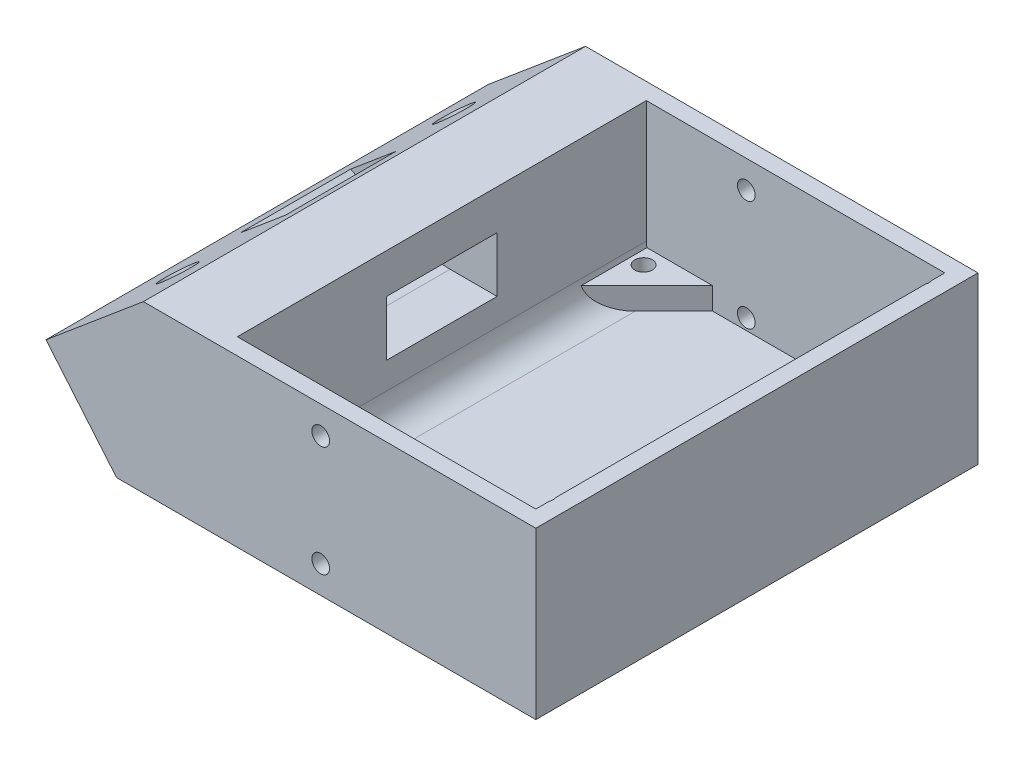
SolidWorks part; units mm, degrees
ref_plane "Спереди" through (0, 0, 0) normal (0, 0, 1) x (1, 0, 0)
ref_plane "Сверху" through (0, 0, 0) normal (0, 1, 0) x (1, 0, 0)
ref_plane "Справа" through (0, 0, 0) normal (1, 0, 0) x (0, 0, -1)
sketch "Sketch1" plane through (0, 0, 0) normal (0, 1, 0) x (1, 0, 0)
  line L1 (30.5, -40) -> (-30.5, -40)
  line L2 (30.5, -40) -> (30.5, 40)
  line L3 (30.5, 40) -> (-30.5, 40)
  line L4 (-30.5, -40) -> (-30.5, 40)
  line L5 (30.5, -40) -> (-30.5, 40) construction
  line L6 (30.5, 40) -> (-30.5, -40) construction
  point P0 (0, 0)
  dimension "D1" = 80
  dimension "D2" = 61
extrude "Boss-Extrude1" add sketch "Sketch1" along normal blind 30
sketch "Sketch2" plane through (0, 30, 0) normal (0, 1, 0) x (1, 0, 0)
  line L0 (30.5, 40) -> (-30.5, 40) construction
  line L1 (-26.5, -37) -> (27.5, -37)
  line L2 (-26.5, -37) -> (-26.5, 37)
  line L3 (-26.5, 37) -> (27.5, 37)
  line L4 (27.5, -37) -> (27.5, 37)
  line L5 (-30.5, -40) -> (30.5, -40) construction
  line L6 (-30.5, 40) -> (-30.5, -40) construction
  line L7 (30.5, -40) -> (30.5, 40) construction
  point P0 (0, 0)
  dimension "D1" = 3
  dimension "D2" = 3
  dimension "D3" = 3
  dimension "D4" = 4
extrude "Cut-Extrude1" cut sketch "Sketch2" against normal blind 27
sketch "Sketch11" plane through (0, 0, 40) normal (0, 0, 1) x (1, 0, 0)
  line L0 (-30.5, 30) -> (-40.5, 30)
  line L1 (-30.5, 0) -> (-58.119, 0)
  line L2 (-30.5, 0) -> (-30.5, 30)
  line L3 (-58.119, 0) -> (-58.119, 15.2159)
  line L4 (-40.5, 30) -> (-58.119, 15.2159)
  line L5 (-40.5, 30) -> (-40.5, 0) construction
  dimension "D1" = 23
  dimension "D2" = 50
  dimension "D3" = 10
extrude "Boss-Extrude3" add sketch "Sketch11" against normal up to surface (80 mm away) up to face at (0, 15, -40)
sketch "Sketch7" plane through (0, 3, 0) normal (0, 1, 0) x (1, 0, 0)
  line L0 (27.5, -25) -> (15.5, -37)
  line L1 (27.5, -37) -> (27.5, 37) construction
  line L2 (-26.5, -37) -> (27.5, -37) construction
  line L3 (15.5, -37) -> (27.5, -37)
  line L4 (27.5, -37) -> (27.5, -25)
  line L5 (27.5, 25) -> (15.5, 37)
  line L6 (27.5, 37) -> (-26.5, 37) construction
  line L7 (15.5, 37) -> (27.5, 37)
  line L8 (27.5, 37) -> (27.5, 25)
  line L9 (-26.5, 25) -> (-14.5, 37)
  line L10 (-26.5, 37) -> (-26.5, -37) construction
  line L11 (-14.5, 37) -> (-26.5, 37)
  line L12 (-26.5, 37) -> (-26.5, 25)
  line L13 (-14.5, -37) -> (-26.5, -25)
  line L14 (-26.5, 37) -> (-26.5, -37) construction
  line L15 (-26.5, -25) -> (-26.5, -37)
  line L16 (-26.5, -37) -> (-14.5, -37)
  dimension "D1" = 12
extrude "Boss-Extrude2" add sketch "Sketch7" along normal blind 4
sketch "Sketch5" plane through (0, 0, 0) normal (0, -1, 0) x (1, 0, 0)
  line L0 (1, -40) -> (1, 40) construction
  line L1 (30.5, -40) -> (-58.119, -40) construction
  line L2 (-58.119, 40) -> (30.5, 40) construction
  line L4 (26, 34) -> (-24, 34) construction
  line L5 (26, 34) -> (26, -34) construction
  line L6 (26, -34) -> (-24, -34) construction
  line L7 (-24, 34) -> (-24, -34) construction
  line L8 (26, 34) -> (-24, -34) construction
  line L9 (26, -34) -> (-24, 34) construction
  circle A0 centre (-24, -34) radius 1.6
  circle A1 centre (-24, 34) radius 1.6
  circle A2 centre (26, 34) radius 1.6
  circle A3 centre (26, -34) radius 1.6
  point P6 (1, 0)
  dimension "D4" = 3.2
  dimension "D1" = 68
  dimension "D2" = 50
  dimension "D3" = 1
extrude "Cut-Extrude3" cut sketch "Sketch5" against normal through all
sketch "Sketch8" plane through (0, 0, 0) normal (0, -1, 0) x (1, 0, 0)
  line L0 (30.5, -40) -> (-58.119, -40) construction
  line L1 (-25.625, 36.8146) -> (-27.25, 34)
  line L2 (-27.25, 34) -> (-25.625, 31.1854)
  line L3 (-25.625, 31.1854) -> (-22.375, 31.1854)
  line L4 (-22.375, 31.1854) -> (-20.75, 34)
  line L5 (-20.75, 34) -> (-22.375, 36.8146)
  line L6 (-22.375, 36.8146) -> (-25.625, 36.8146)
  line L7 (24.375, 36.8146) -> (22.75, 34)
  line L8 (22.75, 34) -> (24.375, 31.1854)
  line L9 (24.375, 31.1854) -> (27.625, 31.1854)
  line L10 (27.625, 31.1854) -> (29.25, 34)
  line L11 (29.25, 34) -> (27.625, 36.8146)
  line L12 (27.625, 36.8146) -> (24.375, 36.8146)
  line L13 (-25.625, -31.1854) -> (-27.25, -34)
  line L14 (-27.25, -34) -> (-25.625, -36.8146)
  line L15 (-25.625, -36.8146) -> (-22.375, -36.8146)
  line L16 (-22.375, -36.8146) -> (-20.75, -34)
  line L17 (-20.75, -34) -> (-22.375, -31.1854)
  line L18 (-22.375, -31.1854) -> (-25.625, -31.1854)
  line L19 (24.375, -31.1854) -> (22.75, -34)
  line L20 (22.75, -34) -> (24.375, -36.8146)
  line L21 (24.375, -36.8146) -> (27.625, -36.8146)
  line L22 (27.625, -36.8146) -> (29.25, -34)
  line L23 (29.25, -34) -> (27.625, -31.1854)
  line L24 (27.625, -31.1854) -> (24.375, -31.1854)
  circle A0 centre (-24, 34) radius 3.25 construction
  circle A1 centre (26, 34) radius 3.25 construction
  circle A2 centre (-24, -34) radius 3.25 construction
  circle A3 centre (26, -34) radius 3.25 construction
  dimension "D1" = 6.5
extrude "Cut-Extrude4" cut sketch "Sketch8" against normal blind 3
sketch "Sketch12" plane through (0, 0, 40) normal (0, 0, 1) x (1, 0, 0)
  line L0 (-58.119, 15.2159) -> (-45.3514, 0)
  line L1 (-58.119, 0) -> (30.5, 0) construction
  line L2 (-45.3514, 0) -> (-58.119, 0)
  line L3 (-58.119, 0) -> (-58.119, 15.2159)
  line L4 (-40.5, 30) -> (-58.119, 15.2159) construction
extrude "Cut-Extrude6" cut sketch "Sketch12" against normal through all
sketch "Sketch16" plane through (-31.5057, 37.5471, 0) normal (-0.6428, 0.766, 0) x (0.766, 0.6428, 0)
  line L0 (-23.2412, 40) -> (-23.2412, -40) construction
  line L1 (-34.7412, 40) -> (-11.7412, 40) construction
  line L2 (-11.7412, -40) -> (-34.7412, -40) construction
  circle A0 centre (-23.2412, 25) radius 3.1
  circle A1 centre (-23.2412, -25) radius 3.1
  point P10 (-23.2412, 0)
  dimension "D1" = 6.2
  dimension "D2" = 50
  dimension "D3" = 25
extrude "Cut-Extrude8" cut sketch "Sketch16" against normal through all
fillet "Fillet1" radius 5 1 edges at (-26.5, 3, 0)
sketch "Sketch17" plane through (-31.5057, 37.5471, 0) normal (-0.6428, 0.766, 0) x (0.766, 0.6428, 0)
  circle A0 centre (-23.2412, -25) radius 6.5
  circle A1 centre (-23.2412, 25) radius 6.5
  dimension "D2" = 13
extrude "Cut-Extrude9" cut sketch "Sketch17" against normal blind 10 from offset 25 offset against normal yes
sketch "Sketch18" plane through (0, 0, 40) normal (0, 0, 1) x (1, 0, 0)
  line L0 (-44.8128, 26.3811) -> (-37.8032, 22.8149)
  line L2 (-40.5, 30) -> (-58.119, 15.2159) construction
  line L3 (-37.8032, 22.8149) -> (-23.8032, 22.8149)
  line L4 (-23.8032, 22.8149) -> (-23.8032, 12.8149)
  line L5 (-23.8032, 12.8149) -> (-39.8032, 12.8149)
  line L6 (-39.8032, 12.8149) -> (-52.9869, 19.5222)
  line L7 (-52.9869, 19.5222) -> (-44.8128, 26.3811)
  dimension "D1" = 10
  dimension "D2" = 14
  dimension "D3" = 16
extrude "Cut-Extrude10" cut sketch "Sketch18" against normal blind 20 from offset 30 offset against normal yes
fillet "Fillet2" radius 20 2 edges at (-39.8032, 12.8149, 0) (-37.8032, 22.8149, 0)
sketch "Sketch19" plane through (0, 0, 40) normal (0, 0, 1) x (1, 0, 0)
  line L0 (-45.3514, 0) -> (-8.4162, 0) construction
  line L1 (-45.3514, 0) -> (30.5, 0) construction
  line L2 (-8.4162, -0.4537) -> (-8.4162, 30) construction
  line L3 (-40.5, 30) -> (30.5, 30) construction
  circle A0 centre (-8.4162, 25) radius 1.6
  circle A1 centre (-8.4162, 5) radius 1.6
  dimension "D2" = 3.2
  dimension "D3" = 20
  dimension "D1" = 36.9352
  dimension "D4" = 5
extrude "Cut-Extrude11" cut sketch "Sketch19" against normal through all
